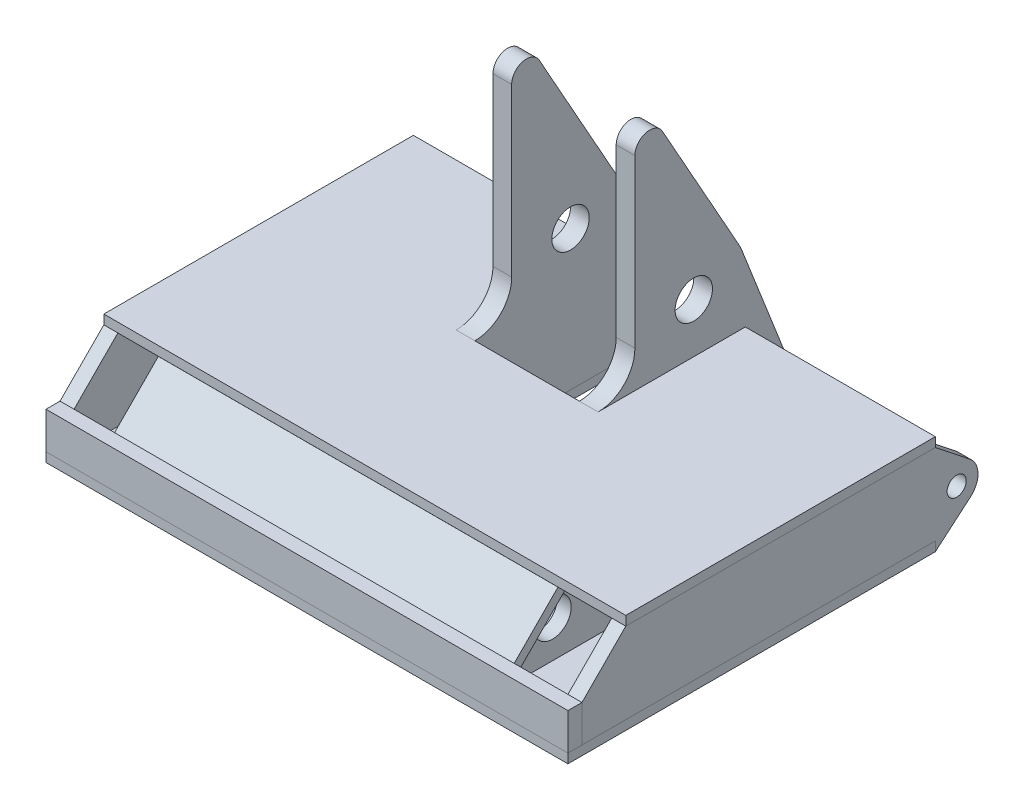
SolidWorks part; units mm, degrees
material "2024-T4"
ref_plane "Front Plane" through (0, 0, 0) normal (0, 0, 1) x (1, 0, 0)
ref_plane "Top Plane" through (0, 0, 0) normal (0, 1, 0) x (1, 0, 0)
ref_plane "Right Plane" through (0, 0, 0) normal (1, 0, 0) x (0, 0, -1)
sketch "Side View" plane through (0, 0, 0) normal (1, 0, 0) x (0, 0, -1)
  line L1 (165, 199.6593) -> (165, 86.35)
  line L3 (140, 55) -> (29.7536, 55)
  line L4 (240, 0) -> (240, 55) construction
  line L5 (0, 0) -> (240, 0)
  line L9 (183.7233, 204.5484) -> (235.5315, 112.1122)
  line L10 (179.9201, 117.2092) -> (110.2141, 38.4935) construction
  line L11 (29.7536, 55) -> (140, 55)
  line L12 (29.7536, 55) -> (29.7536, 61.35) construction
  line L13 (29.7536, 61.35) -> (140, 61.35) construction
  line L14 (140, 55) -> (140, 61.35)
  line L15 (0, 0) -> (240, 0) construction
  line L16 (0, 0) -> (0, -6.35) construction
  line L17 (0, -6.35) -> (240, -6.35) construction
  line L18 (240, 0) -> (240, -6.35) construction
  line L19 (223.5253, 67.0883) -> (135.9217, 8.9446) construction
  line L20 (240, 55) -> (240, 0) construction
  line L21 (240, 0) -> (240, -6.35)
  line L22 (240, 55) -> (230.475, 55) construction
  line L23 (230.475, 55) -> (230.475, 0) construction
  line L24 (13.588, 51.1116) -> (-9.525, 27.8072) construction
  line L25 (240, -6.35) -> (263.8895, 13.9507)
  line L26 (267.9974, 30.2982) -> (237.5799, 107.7886)
  line L27 (13.588, 51.1116) -> (167.8998, 206.7011) construction
  line L28 (190.9625, 46.4) -> (39.5125, 46.4) construction
  line L29 (39.5125, 25.4) -> (190.9625, 25.4) construction
  line L30 (190.9625, 4.4) -> (39.5125, 4.4) construction
  line L31 (-9.525, 25) -> (-9.525, -6.35) construction
  line L32 (-9.525, -6.35) -> (0, -6.35) construction
  line L33 (0, 0) -> (0, 25)
  line L34 (0, 25) -> (29.7536, 55)
  line L35 (-9.525, 25) -> (0, 25) construction
  line L36 (-4.5086, 29.4716) -> (25.245, 59.4716) construction
  line L37 (0, 25) -> (-4.5086, 29.4716) construction
  line L38 (29.7536, 55) -> (25.245, 59.4716) construction
  circle A1 centre (205, 95) radius 12.7
  circle A2 centre (205, 95) radius 100 construction
  arc A3 (183.7233, 204.5484) -> (165, 199.6593) centre (175, 199.6593) ccw
  arc A4 (140, 61.35) -> (165, 86.35) centre (140, 86.35) ccw
  circle A5 centre (125, 25.4) radius 19.75 construction
  circle A6 centre (205, 95) radius 33.5 construction
  circle A7 centre (39.5125, 25.4) radius 36.5125 construction
  circle A8 centre (190.9625, 25.4) radius 36.5125 construction
  circle A9 centre (254.5, 25) radius 6.5
  arc A11 (263.8895, 13.9507) -> (267.9974, 30.2982) centre (254.5, 25) ccw
  arc A13 (237.5799, 107.7886) -> (235.5315, 112.1122) centre (205, 95) ccw
  circle A14 centre (190.9625, 25.4) radius 21 construction
  circle A15 centre (39.5125, 25.4) radius 21 construction
  point P16 (240, 0)
  point P24 (165, 237.9546)
  point P40 (217.1923, 0)
  point P45 (164.7327, 0)
  point P49 (65.7423, 0)
  point P50 (13.2827, 0)
  dimension "D1" = 25.4
  dimension "D3" = 200
  dimension "D8" = 10
  dimension "D11" = 39.5
  dimension "D15" = 67
  dimension "D17" = 73.025
  dimension "D16" = 13
  dimension "D29" = 73.025
  dimension "D31" = 42
  dimension "D32" = 42
  dimension "D28" = 35
  dimension "D2" = 55
  dimension "D9" = 6.35
  dimension "D10" = 25
  dimension "D14" = 40
  dimension "D5" = 5
  dimension "D4" = 35
  dimension "D18" = 4.7625
  dimension "D7" = 5
  dimension "D20" = 3
  dimension "D22" = 25
  dimension "D26" = 9.525
  dimension "D13" = 80
  dimension "D19" = 3
  dimension "D6" = 240
  dimension "D24" = 8
  dimension "D25" = 8
  dimension "D27" = 25
  dimension "D30" = 4.7625
  dimension "D34" = 151.45
  dimension "D21" = 6.35
sketch "Top View" plane through (0, 0, 0) normal (0, 1, 0) x (1, 0, 0)
  line L0 (0, 120) -> (0, 0) construction
  line L1 (177.25, 0) -> (167.725, 0)
  line L2 (177.25, 0) -> (177.25, 240)
  line L3 (177.25, 240) -> (35.5, 240)
  line L4 (-177.25, 0) -> (-177.25, 240)
  line L5 (177.25, 0) -> (-177.25, 240) construction
  line L6 (177.25, 240) -> (-177.25, 0) construction
  line L9 (-35.5, 240) -> (-35.5, 0)
  line L11 (35.5, 240) -> (35.5, 0)
  line L13 (-167.725, 230.475) -> (-167.725, 0)
  line L15 (-117.725, 230.475) -> (-117.725, 0)
  line L17 (167.725, 230.475) -> (117.725, 230.475)
  line L18 (167.725, 230.475) -> (167.725, 0)
  line L19 (-35.5, 240) -> (-177.25, 240)
  line L20 (-167.725, 0) -> (-177.25, 0)
  line L22 (167.725, 230.475) -> (48.2, 230.475)
  line L26 (-48.2, 230.475) -> (-167.725, 230.475)
  line L29 (167.725, 0) -> (-108.2, 0)
  line L33 (-150.8375, 190.9625) -> (-150.8375, 229.0625) construction
  line L35 (-161.95, 77.6125) -> (-161.95, 1.4125) construction
  line L36 (108.2, 165.9625) -> (58.2, 165.9625) construction
  line L37 (-108.2, 215.9625) -> (-58.2, 215.9625) construction
  line L38 (-108.2, 215.9625) -> (-108.2, 165.9625) construction
  line L39 (-108.2, 165.9625) -> (-58.2, 165.9625) construction
  line L40 (-58.2, 215.9625) -> (-58.2, 165.9625) construction
  line L41 (58.2, 215.9625) -> (58.2, 165.9625) construction
  line L42 (108.2, 215.9625) -> (58.2, 215.9625) construction
  line L43 (108.2, 215.9625) -> (108.2, 165.9625) construction
  line L44 (161.95, 152.8625) -> (139.725, 152.8625) construction
  line L45 (-161.95, 229.0625) -> (-139.725, 229.0625) construction
  line L46 (-161.95, 229.0625) -> (-161.95, 152.8625) construction
  line L47 (-161.95, 152.8625) -> (-139.725, 152.8625) construction
  line L48 (-139.725, 229.0625) -> (-139.725, 152.8625) construction
  line L49 (-161.95, 229.0625) -> (-139.725, 152.8625) construction
  line L50 (-161.95, 152.8625) -> (-139.725, 229.0625) construction
  line L51 (139.725, 229.0625) -> (139.725, 152.8625) construction
  line L52 (161.95, 229.0625) -> (139.725, 229.0625) construction
  line L53 (161.95, 229.0625) -> (161.95, 152.8625) construction
  line L54 (-108.2, 240) -> (-108.2, 0) construction
  line L56 (-139.725, 77.6125) -> (-139.725, 1.4125) construction
  line L57 (-48.2, 230.475) -> (-48.2, 0)
  line L58 (48.2, 230.475) -> (48.2, 0)
  line L59 (-108.2, 0) -> (-167.725, 0)
  line L60 (-117.725, 230.475) -> (-117.725, -9.525) construction
  line L61 (105.4111, 240) -> (167.725, 0) construction
  line L62 (-35.5, 240) -> (35.5, 240)
  line L63 (-48.2, 230.475) -> (48.2, 230.475) construction
  line L65 (167.725, 240) -> (105.4111, 240) construction
  line L66 (-167.725, 240) -> (-108.2, 240) construction
  line L67 (-167.725, 230.475) -> (-117.725, 230.475) construction
  line L68 (-161.95, 1.4125) -> (-139.725, 1.4125) construction
  line L69 (-161.95, 39.5125) -> (-139.725, 39.5125) construction
  line L70 (-177.25, 0) -> (-177.25, -9.525)
  line L71 (-119.725, 9.5125) -> (-119.725, 69.5125) construction
  line L72 (-119.725, 160.9625) -> (-139.725, 160.9625) construction
  line L73 (-119.725, 160.9625) -> (-119.725, 220.9625) construction
  line L74 (-119.725, 220.9625) -> (-139.725, 220.9625) construction
  line L75 (-139.725, 160.9625) -> (-139.725, 220.9625) construction
  line L76 (-119.725, 160.9625) -> (-139.725, 220.9625) construction
  line L77 (-119.725, 220.9625) -> (-139.725, 160.9625) construction
  line L78 (-119.725, 9.5125) -> (-139.725, 9.5125) construction
  line L79 (-139.725, 9.5125) -> (-139.725, 69.5125) construction
  line L80 (-119.725, 69.5125) -> (-139.725, 69.5125) construction
  line L81 (-108.2, 230.475) -> (-108.2, 0)
  line L82 (-161.95, 77.6125) -> (-139.725, 77.6125) construction
  line L83 (-161.95, 77.6125) -> (-139.725, 77.6125) construction
  line L84 (-177.25, -9.525) -> (177.25, -9.525)
  line L85 (48.2, 145) -> (117.5, 145) construction
  line L86 (48.2, 145) -> (48.2, 105) construction
  line L87 (48.2, 105) -> (117.5, 105) construction
  line L88 (117.5, 145) -> (117.5, 105) construction
  line L89 (1.5875, 105) -> (-23.8125, 105) construction
  line L90 (1.5875, 105) -> (1.5875, 305) construction
  line L91 (1.5875, 305) -> (-23.8125, 305) construction
  line L92 (-23.8125, 105) -> (-23.8125, 305) construction
  line L93 (1.5875, 105) -> (-23.8125, 305) construction
  line L94 (1.5875, 305) -> (-23.8125, 105) construction
  line L95 (177.25, -9.525) -> (177.25, 0)
  line L96 (0, 105) -> (0, 305) construction
  line L97 (-11.1125, 205) -> (11.1125, 205) construction
  line L98 (20.6375, 171.5) -> (1.5875, 171.5) construction
  line L99 (20.6375, 171.5) -> (20.6375, 238.5) construction
  line L100 (20.6375, 238.5) -> (1.5875, 238.5) construction
  line L101 (1.5875, 171.5) -> (1.5875, 238.5) construction
  line L102 (20.6375, 171.5) -> (1.5875, 238.5) construction
  line L103 (20.6375, 238.5) -> (1.5875, 171.5) construction
  line L104 (180.0389, -9.525) -> (-117.725, -9.525) construction
  line L105 (117.725, 230.475) -> (180.0389, -9.525) construction
  line L106 (119.725, 160.9625) -> (139.725, 160.9625) construction
  line L107 (119.725, 160.9625) -> (119.725, 220.9625) construction
  line L108 (119.725, 220.9625) -> (139.725, 220.9625) construction
  line L109 (108.2, 230.475) -> (108.2, 0)
  line L110 (117.725, 230.475) -> (117.725, 0)
  line L111 (119.725, 9.5125) -> (119.725, 69.5125) construction
  line L112 (119.725, 69.5125) -> (139.725, 69.5125) construction
  line L113 (119.725, 9.5125) -> (139.725, 9.5125) construction
  line L114 (161.95, 1.4125) -> (139.725, 1.4125) construction
  line L115 (161.95, 77.6125) -> (139.725, 77.6125) construction
  line L116 (161.95, 77.6125) -> (161.95, 1.4125) construction
  line L117 (139.725, 77.6125) -> (139.725, 1.4125) construction
  line L118 (-167.725, 230.475) -> (-167.725, 240)
  line L119 (-48.2, 230.475) -> (-48.2, 240)
  line L120 (48.2, 230.475) -> (48.2, 240)
  line L121 (167.725, 230.475) -> (167.725, 240)
  line L122 (0, 171.5) -> (0, 238.5) construction
  line L123 (-35.5, 145) -> (35.5, 145)
  line L125 (-107.2, 162) -> (-51.2, 162) construction
  line L126 (-107.2, 162) -> (-107.2, 2) construction
  line L127 (-107.2, 2) -> (-51.2, 2) construction
  line L128 (-51.2, 162) -> (-51.2, 2) construction
  line L129 (-35.5, 104) -> (35.5, 104)
  line L130 (-35.5, 104) -> (-35.5, 94.475)
  line L131 (-35.5, 94.475) -> (35.5, 94.475)
  line L132 (35.5, 104) -> (35.5, 94.475)
  point P0 (0, 0)
  point P44 (-150.8375, 190.9625)
  point P45 (-167.725, 115.2375)
  point P58 (-129.725, 190.9625)
  point P60 (-58.2, 190.9625)
  point P76 (0, 205)
  point P77 (11.1125, 205)
  point P78 (-11.1125, 205)
  point P87 (117.5, 125)
  dimension "D5" = 50
  dimension "D6" = 9.525
  dimension "D10" = 22.225
  dimension "D11" = 76.2
  dimension "D12" = 50
  dimension "D8" = 9.525
  dimension "D15" = 12.7
  dimension "D7" = 50
  dimension "D4" = 20
  dimension "D14" = 2
  dimension "D16" = 60
  dimension "D3" = 71
  dimension "D18" = 9.525
  dimension "D19" = 40
  dimension "D21" = 25.4
  dimension "D22" = 19.05
  dimension "D24" = 9.525
  dimension "D25" = 60
  dimension "D23" = 56
  dimension "D26" = 160
  dimension "D27" = 2
  dimension "D28" = 3
  dimension "D29" = 9.525
  dimension "D30" = 1
  dimension "D31" = 60
  dimension "D32" = 354.5
  dimension "D20" = 82
  dimension "D33" = 240
  dimension "D9" = 9.525
  dimension "D13" = 2
  dimension "D17" = 2
ref_plane "Left Weapon Wall Plane" through (-35.5, 0, 0) normal (1, 0, 0) x (0, 0, -1)
ref_plane "Right Weapon Wall Plane" through (35.5, 0, 0) normal (1, 0, 0) x (0, 0, -1)
ref_plane "Front Wall Plane" through (0, 0, -240) normal (0, 0, 1) x (1, 0, 0)
ref_plane "Rear Wall Plane" through (0, 0, 9.525) normal (0, 0, 1) x (1, 0, 0)
ref_plane "Left Motor Wall Plane" through (-108.2, 0, 0) normal (1, 0, 0) x (0, 0, -1)
ref_plane "Right Motor Wall Plane" through (108.2, 0, 0) normal (1, 0, 0) x (0, 0, -1)
ref_plane "Left Outside Wall Plane" through (-177.25, 0, 0) normal (1, 0, 0) x (0, 0, -1)
ref_plane "Wheel Center" through (-150.8375, 0, 0) normal (1, 0, 0) x (0, 0, -1)
ref_plane "Angled Back Plane" through (0, 12.3969, 12.4996) normal (0, -0.7042, -0.71) x (0, 0.71, -0.7042)
ref_plane "Top Plate Plane" through (0, 55, 0) normal (0, 1, 0) x (1, 0, 0)
ref_plane "Shielding Plate Plane" through (0, 0, -104) normal (0, 0, 1) x (1, 0, 0)
sketch "Sketch14" plane through (0, 0, -104) normal (0, 0, 1) x (1, 0, 0)
  line L1 (-35.5, 0) -> (35.5, 0)
  line L2 (-35.5, 0) -> (-35.5, 55)
  line L3 (-35.5, 55) -> (35.5, 55)
  line L4 (35.5, 0) -> (35.5, 55)
extrude "Boss-Extrude9" add sketch "Sketch14" along normal up to vertex (9.525 mm away) up to point (-35.5, 0, -94.475)
sketch "Sketch2" plane through (0, 0, 0) normal (0, 1, 0) x (1, 0, 0)
  line L0 (177.25, -9.525) -> (177.25, 0) construction
  line L1 (-177.25, 0) -> (-177.25, -9.525) construction
  line L2 (-177.25, -9.525) -> (177.25, -9.525) construction
  line L3 (177.25, 0) -> (177.25, 240) construction
  line L4 (177.25, 240) -> (35.5, 240) construction
  line L5 (35.5, 240) -> (35.5, 0) construction
  line L6 (-35.5, 145) -> (35.5, 145) construction
  line L7 (-35.5, 240) -> (-35.5, 0) construction
  line L8 (-35.5, 240) -> (-177.25, 240) construction
  line L9 (-177.25, 0) -> (-177.25, 240) construction
  line L10 (177.25, -9.525) -> (177.25, 0)
  line L11 (-177.25, 0) -> (-177.25, -9.525)
  line L12 (-177.25, -9.525) -> (177.25, -9.525)
  line L13 (177.25, 0) -> (177.25, 240)
  line L14 (177.25, 240) -> (35.5, 240)
  line L15 (35.5, 240) -> (35.5, 145)
  line L16 (-35.5, 145) -> (35.5, 145)
  line L17 (-35.5, 240) -> (-35.5, 145)
  line L18 (-35.5, 240) -> (-177.25, 240)
  line L19 (-177.25, 0) -> (-177.25, 240)
  line L20 (-161.95, 1.4125) -> (-139.725, 1.4125) construction
  line L21 (-139.725, 77.6125) -> (-139.725, 1.4125) construction
  line L22 (-161.95, 77.6125) -> (-139.725, 77.6125) construction
  line L23 (-161.95, 77.6125) -> (-161.95, 1.4125) construction
  line L24 (-139.725, 229.0625) -> (-139.725, 152.8625) construction
  line L25 (-163.95, 219.1923) -> (-137.725, 219.1923)
  line L26 (-137.725, 219.1923) -> (-137.725, 162.7327)
  line L27 (-161.95, 229.0625) -> (-161.95, 152.8625) construction
  line L28 (-161.95, 1.4125) -> (-139.725, 1.4125) construction
  line L29 (-139.725, 77.6125) -> (-139.725, 1.4125) construction
  line L30 (-161.95, 77.6125) -> (-139.725, 77.6125) construction
  line L31 (-161.95, 77.6125) -> (-161.95, 1.4125) construction
  line L32 (-139.725, 217.1923) -> (-139.725, 164.7327) construction
  line L35 (-161.95, 217.1923) -> (-161.95, 164.7327) construction
  line L36 (-161.95, 217.1923) -> (-139.725, 217.1923) construction
  line L37 (-150.8375, 190.9625) -> (-129.725, 190.9625) construction
  line L38 (-161.95, 164.7327) -> (-139.725, 164.7327) construction
  line L39 (-163.95, 162.7327) -> (-137.725, 162.7327)
  line L40 (-163.95, 219.1923) -> (-163.95, 162.7327)
  line L41 (-137.725, 67.7423) -> (-137.725, 11.2827)
  line L42 (-163.95, 67.7423) -> (-137.725, 67.7423)
  line L43 (-163.95, 67.7423) -> (-163.95, 11.2827)
  line L44 (-163.95, 11.2827) -> (-137.725, 11.2827)
  line L45 (-150.8375, 39.5125) -> (-129.725, 39.5125) construction
  line L46 (-161.95, 39.5125) -> (-139.725, 39.5125) construction
  dimension "D1" = 2
  dimension "D2" = 2
extrude "Bottom Plate" add sketch "Sketch2" against normal up to vertex (6.35 mm away) up to point (0, -6.35, 0)
sketch "Sketch3" plane through (-35.5, 0, 0) normal (1, 0, 0) x (0, 0, -1)
  line L0 (140, 55) -> (29.7536, 55) construction
  line L2 (140, 55) -> (140, 61.35) construction
  line L3 (165, 199.6593) -> (165, 86.35) construction
  line L4 (183.7233, 204.5484) -> (235.5315, 112.1122) construction
  line L7 (0, 0) -> (240, 0) construction
  line L8 (0, 0) -> (0, 25) construction
  line L9 (0, 25) -> (29.7536, 55) construction
  line L10 (140, 55) -> (29.7536, 55)
  line L12 (140, 55) -> (140, 61.35)
  line L13 (165, 199.6593) -> (165, 86.35)
  line L14 (183.7233, 204.5484) -> (235.5315, 112.1122)
  line L17 (0, 0) -> (240, 0)
  line L18 (0, 0) -> (0, 25)
  line L19 (0, 25) -> (29.7536, 55)
  line L20 (240, 0) -> (240, -6.35) construction
  line L21 (240, -6.35) -> (263.8895, 13.9507) construction
  line L22 (267.9974, 30.2982) -> (237.5799, 107.7886) construction
  line L23 (240, 0) -> (240, -6.35)
  line L24 (240, -6.35) -> (263.8895, 13.9507)
  line L25 (267.9974, 30.2982) -> (237.5799, 107.7886)
  arc A0 (140, 61.35) -> (165, 86.35) centre (140, 86.35) ccw construction
  arc A1 (183.7233, 204.5484) -> (165, 199.6593) centre (175, 199.6593) ccw construction
  arc A3 (140, 61.35) -> (165, 86.35) centre (140, 86.35) ccw
  arc A4 (183.7233, 204.5484) -> (165, 199.6593) centre (175, 199.6593) ccw
  circle A6 centre (205, 95) radius 12.7 construction
  circle A7 centre (205, 95) radius 12.7
  arc A8 (263.8895, 13.9507) -> (267.9974, 30.2982) centre (254.5, 25) ccw construction
  arc A9 (263.8895, 13.9507) -> (267.9974, 30.2982) centre (254.5, 25) ccw
  arc A12 (237.5799, 107.7886) -> (235.5315, 112.1122) centre (205, 95) ccw construction
  arc A13 (237.5799, 107.7886) -> (235.5315, 112.1122) centre (205, 95) ccw
  circle A14 centre (254.5, 25) radius 6.5 construction
  circle A15 centre (254.5, 25) radius 6.5
extrude "Left Weapon Wall" add sketch "Sketch3" against normal up to vertex (12.7 mm away) separate body contours L14 A4 L13 A3 L12 L10 L19 L18 L17 A7 region at (-35.5, 60.3075, -158.2222) up to point (-48.2, 0, 0)
sketch "Sketch5" plane through (-177.25, 0, 0) normal (1, 0, 0) x (0, 0, -1)
  line L1 (0, 0) -> (240, 0) construction
  line L2 (0, 0) -> (0, 25) construction
  line L3 (0, 25) -> (29.7536, 55) construction
  line L4 (140, 55) -> (29.7536, 55) construction
  line L6 (0, 0) -> (240, 0)
  line L7 (0, 0) -> (0, 25)
  line L8 (0, 25) -> (29.7536, 55)
  line L9 (240, 55) -> (29.7536, 55)
  line L10 (240, -6.35) -> (263.8895, 13.9507) construction
  line L11 (240, 0) -> (240, -6.35) construction
  line L12 (240, -6.35) -> (263.8895, 13.9507)
  line L13 (240, 0) -> (240, -6.35)
  line L14 (263.5082, 36.3623) -> (240, 55)
  line L15 (240, 55) -> (230.475, 55) construction
  arc A0 (263.8895, 13.9507) -> (267.9974, 30.2982) centre (254.5, 25) ccw construction
  arc A1 (263.8895, 13.9507) -> (263.5082, 36.3623) centre (254.5, 25) ccw
  circle A2 centre (254.5, 25) radius 6.5 construction
  circle A3 centre (254.5, 25) radius 6.5
  point P6 (39.5125, 25.4)
  point P8 (190.9625, 25.4)
extrude "Left Wall" add sketch "Sketch5" along normal up to vertex (9.525 mm away) separate body up to point (-167.725, 0, 0)
sketch "Sketch6" plane through (-108.2, 0, 0) normal (1, 0, 0) x (0, 0, -1)
  line L1 (240, 0) -> (-9.525, 0) construction
  line L2 (0, 0) -> (0, 25) construction
  line L3 (0, 25) -> (29.7536, 55) construction
  line L4 (140, 55) -> (29.7536, 55) construction
  line L6 (230.475, 0) -> (0, 0)
  line L7 (0, 0) -> (0, 25)
  line L8 (0, 25) -> (29.7536, 55)
  line L9 (230.475, 55) -> (29.7536, 55)
  line L10 (230.475, 55) -> (230.475, 0) construction
  line L11 (230.475, 55) -> (230.475, 0)
extrude "Left Motor Wall" add sketch "Sketch6" against normal up to vertex (9.525 mm away) separate body up to point (-117.725, 0, 0)
sketch "Sketch7" plane through (0, 0, 9.525) normal (0, 0, 1) x (1, 0, 0)
  line L1 (-177.25, 0) -> (177.25, 0) construction
  line L2 (-177.25, 0) -> (177.25, 0)
  line L4 (-177.25, 0) -> (177.25, 0)
  line L5 (-177.25, 0) -> (-177.25, 25)
  line L6 (-177.25, 25) -> (177.25, 25)
  line L7 (177.25, 0) -> (177.25, 25)
  point P0 (0, 25)
extrude "Rear Wall" add sketch "Sketch7" against normal up to vertex (9.525 mm away) separate body contours L2 L7 L6 L5 region at (0, 12.5, 9.525) up to point (0, 0, 0)
sketch "Sketch8" plane through (0, 0, -240) normal (0, 0, 1) x (1, 0, 0)
  line L0 (-35.5, 0) -> (-177.25, 0) construction
  line L1 (-48.2, 0) -> (-167.725, 0)
  line L3 (-48.2, 0) -> (-167.725, 0)
  line L5 (-48.2, 55) -> (-167.725, 55)
  line L8 (-48.2, 55) -> (-48.2, 0)
  line L9 (-167.725, 0) -> (-167.725, 55)
  point P0 (0, 55)
  point P10 (-167.725, 0)
extrude "Boss-Extrude6" add sketch "Sketch8" along normal up to vertex (9.525 mm away) separate body contours L1 L5 region at (-107.9625, 27.5, -240) up to point (-48.2, 0, -230.475)
mirror "Mirror1" about plane through (0, 0, 0) normal (1, 0, 0) of bodies 103 106 102 104
sketch "Sketch10" plane through (108.2, 0, 0) normal (-1, 0, 0) x (0, 0, 1)
  circle A0 centre (-190.9625, 25.4) radius 12.7
  circle A1 centre (-39.5125, 25.4) radius 12.7
  circle A2 centre (-125, 25.4) radius 20.5
  dimension "D1" = 25.4
  dimension "D2" = 41
extrude "Cut-Extrude1" cut sketch "Sketch10" against normal up to next (9.525 mm away)
sketch "Sketch11" plane through (-117.725, 0, 0) normal (-1, 0, 0) x (0, 0, 1)
  circle A0 centre (-39.5125, 25.4) radius 12.7 construction
  circle A1 centre (-190.9625, 25.4) radius 12.7 construction
  circle A2 centre (-39.5125, 25.4) radius 12.7
  circle A3 centre (-190.9625, 25.4) radius 12.7
extrude "Cut-Extrude2" cut sketch "Sketch11" against normal up to next (9.525 mm away)
sketch "Sketch12" plane through (0, 12.3969, 12.4996) normal (0, -0.7042, -0.71) x (0, 0.71, -0.7042)
  line L0 (162.2971, -117.725) -> (0, -117.725) construction
  line L1 (60.003, 135.725) -> (17.7504, 135.725)
  line L2 (60.003, 135.725) -> (60.003, -135.725)
  line L3 (60.003, -135.725) -> (17.7504, -135.725)
  line L4 (17.7504, 135.725) -> (17.7504, -135.725)
  line L8 (0, 0) -> (60.003, 0) construction
  line L9 (-4.5086, 0) -> (164.4959, 0) construction
  dimension "D1" = 18
extrude "Rear Angled Plate" add sketch "Sketch12" against normal up to vertex (6.35 mm away) separate body up to point (0, 59.4716, -25.245)
sketch "Sketch13" plane through (0, 55, 0) normal (0, 1, 0) x (1, 0, 0)
  line L25 (0, 140) -> (0, 29.7536) construction
  line L26 (-48.2, 230.475) -> (-48.2, 0) construction
  line L27 (-48.2, 230.475) -> (-48.2, 240) construction
  line L28 (-35.5, 240) -> (-177.25, 240) construction
  line L29 (-177.25, 0) -> (-177.25, 240) construction
  line L31 (177.25, 29.7536) -> (177.25, 240)
  line L33 (48.2, 240) -> (177.25, 240)
  line L34 (0, 140) -> (0, 29.7536) construction
  line L35 (-48.2, 230.475) -> (-48.2, 140)
  line L36 (-48.2, 230.475) -> (-48.2, 240)
  line L37 (-48.2, 240) -> (-177.25, 240)
  line L38 (-177.25, 29.7536) -> (-177.25, 240)
  line L40 (-48.2, 140) -> (48.2, 140)
  line L43 (-177.25, 29.7536) -> (177.25, 29.7536)
  line L44 (48.2, 230.475) -> (48.2, 240)
  line L45 (48.2, 230.475) -> (48.2, 140)
  line L50 (-135.725, 29.7536) -> (135.725, 29.7536) construction
extrude "Top Plate" add sketch "Sketch13" along normal up to vertex (6.35 mm away) separate body up to point (0, 61.35, -29.7536)
sketch "Sketch15" plane through (48.2, 0, 0) normal (1, 0, 0) x (0, 0, -1)
  circle A0 centre (125, 25.4) radius 19.75 construction
  circle A1 centre (125, 25.4) radius 19.75 construction
  circle A2 centre (125, 25.4) radius 20.5
  dimension "D1" = 41
extrude "Cut-Extrude3" cut sketch "Sketch15" against normal up to surface (12.7 mm away) up to face at (35.5, 25, -261)
equation "\"D8@Top View\"=\"D9@Top View\""
equation "\"D18@Top View\"=\"D8@Top View\""
equation "\"D24@Top View\"=\"D8@Top View\""
equation "\"D19@Side View\"=\"D20@Side View\""
equation "\"D29@Top View\"=\"D18@Top View\""
equation "\"D30@Side View\"=\"D18@Side View\""
equation "\"D31@Side View\"=\"D32@Side View\""
